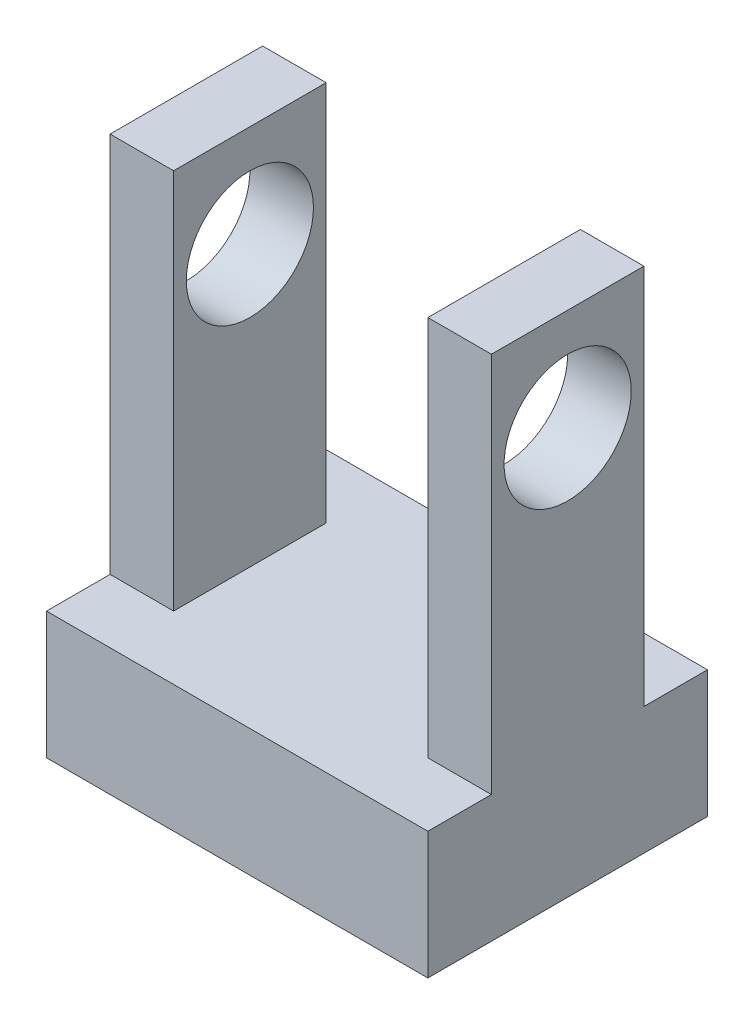
SolidWorks part; units mm, degrees
ref_plane "Front Plane" through (0, 0, 0) normal (0, 0, 1) x (1, 0, 0)
ref_plane "Top Plane" through (0, 0, 0) normal (0, 1, 0) x (1, 0, 0)
ref_plane "Right Plane" through (0, 0, 0) normal (1, 0, 0) x (0, 0, -1)
sketch "Sketch1" plane through (0, 0, 0) normal (0, 1, 0) x (1, 0, 0)
  line L1 (-65.6376, -29.2634) -> (-35.6376, -29.2634)
  line L2 (-65.6376, -29.2634) -> (-65.6376, -51.2634)
  line L3 (-65.6376, -51.2634) -> (-35.6376, -51.2634)
  line L4 (-35.6376, -29.2634) -> (-35.6376, -51.2634)
  line L5 (-65.6376, -34.2634) -> (-60.6376, -34.2634)
  line L6 (-65.6376, -34.2634) -> (-65.6376, -46.2634)
  line L7 (-65.6376, -46.2634) -> (-60.6376, -46.2634)
  line L8 (-60.6376, -34.2634) -> (-60.6376, -46.2634)
  line L9 (-35.6376, -34.2634) -> (-40.6376, -34.2634)
  line L10 (-35.6376, -34.2634) -> (-35.6376, -46.2634)
  line L11 (-35.6376, -46.2634) -> (-40.6376, -46.2634)
  line L12 (-40.6376, -34.2634) -> (-40.6376, -46.2634)
  point P12 (0, 0)
  dimension "D1" = 5
  dimension "D2" = 5
  dimension "D3" = 5
  dimension "D4" = 30
  dimension "D5" = 12
  dimension "D6" = 5
extrude "Boss-Extrude1" add sketch "Sketch1" along normal blind 10 contours L1 L4 L3 L2
extrude "Boss-Extrude2" add sketch "Sketch1<4>" along normal blind 40 contours L8 L7 L6 L5 | L12 L11 L10 L9
sketch "Sketch1<4>" plane through (0, 0, 0) normal (0, 1, 0) x (1, 0, 0) same geometry as "Sketch1"
sketch "Sketch2" plane through (-65.6376, 0, 0) normal (-1, 0, 0) x (0, 0, 1)
  line L0 (34.2634, 40) -> (46.2634, 40) construction
  circle A0 centre (40.2634, 32) radius 5
  point P2 (0, 0)
  point P5 (40.2634, 40)
  dimension "D1" = 10
  dimension "D2" = 8
extrude "Cut-Extrude1" cut sketch "Sketch2" against normal blind 40 contours A0
